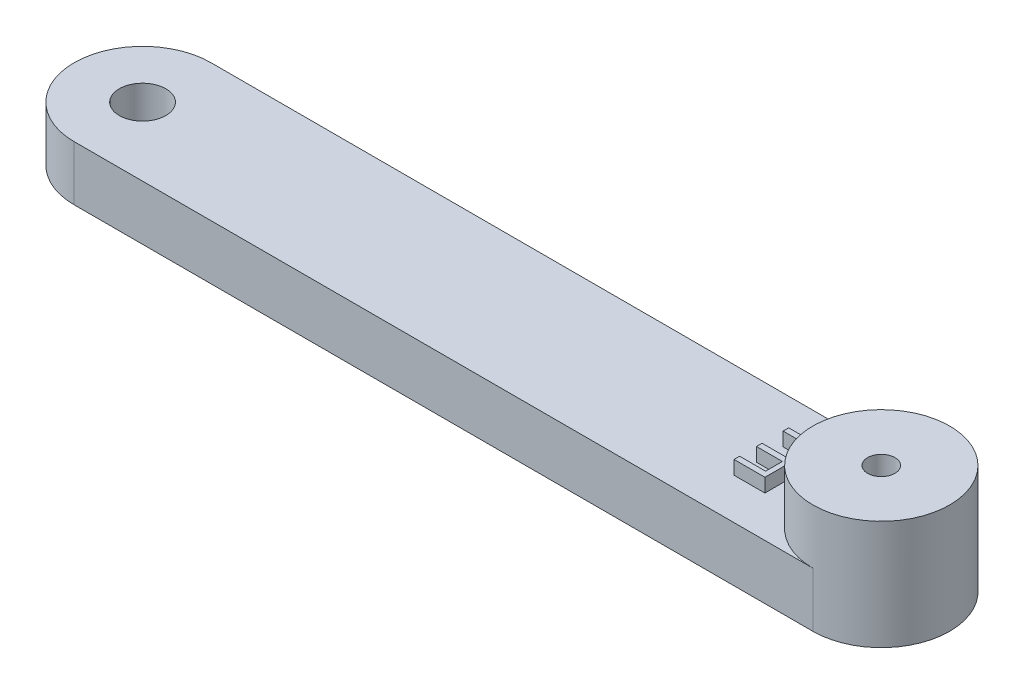
SolidWorks part; units mm, degrees
ref_plane "Plano frontal" through (0, 0, 0) normal (0, 0, 1) x (1, 0, 0)
ref_plane "Plano superior" through (0, 0, 0) normal (0, 1, 0) x (1, 0, 0)
ref_plane "Plano direito" through (0, 0, 0) normal (1, 0, 0) x (0, 0, -1)
sketch "Esboço1" plane through (0, 0, 0) normal (0, 1, 0) x (1, 0, 0)
  line L0 (-13.5, 0) -> (13.5, 0) construction
  line L1 (-13.5, 2.5) -> (13.5, 2.5)
  line L2 (-13.5, -2.5) -> (13.5, -2.5)
  arc A0 (-13.5, 2.5) -> (-13.5, -2.5) centre (-13.5, 0) ccw
  arc A1 (13.5, -2.5) -> (13.5, 2.5) centre (13.5, 0) ccw
  point P3 (0, 0)
  dimension "D1" = 27
  dimension "D2" = 5
extrude "Ressalto-extrusão1" add sketch "Esboço1" along normal blind 2
sketch "Esboço2" plane through (0, 2, 0) normal (0, 1, 0) x (1, 0, 0)
  circle A0 centre (-13.5, 0) radius 0.85
  arc A1 (-13.5, 2.5) -> (-13.5, -2.5) centre (-13.5, 0) ccw construction
  dimension "D1" = 1.7
extrude "Corte-extrusão1" cut sketch "Esboço2" against normal through all
sketch "Esboço4" plane through (0, 2, 0) normal (0, 1, 0) x (1, 0, 0)
  circle A0 centre (13.5, 0) radius 2.5
  arc A1 (13.5, -2.5) -> (13.5, 2.5) centre (13.5, 0) ccw construction
extrude "Ressalto-extrusão2" add sketch "Esboço4" along normal blind 2
sketch "Esboço3" plane through (0, 4, 0) normal (0, 1, 0) x (1, 0, 0)
  circle A0 centre (13.5, 0) radius 0.5
  arc A1 (13.5, 2.5) -> (13.5, -2.5) centre (13.5, 0) ccw construction
  dimension "D1" = 1
extrude "Corte-extrusão2" cut sketch "Esboço3" against normal up to next
sketch "Esboço5" plane through (0, 2, 0) normal (0, 1, 0) x (1, 0, 0)
  line L0 (8.5209, 1) -> (10.997, 1) construction
  line L1 (13.5, 2.5) -> (-13.5, 2.5) construction
  text T0 "E" font "Century Gothic" height 2
  dimension "D1" = 1.5
extrude "Ressalto-extrusão3" add sketch "Esboço5" along normal blind 0.5
